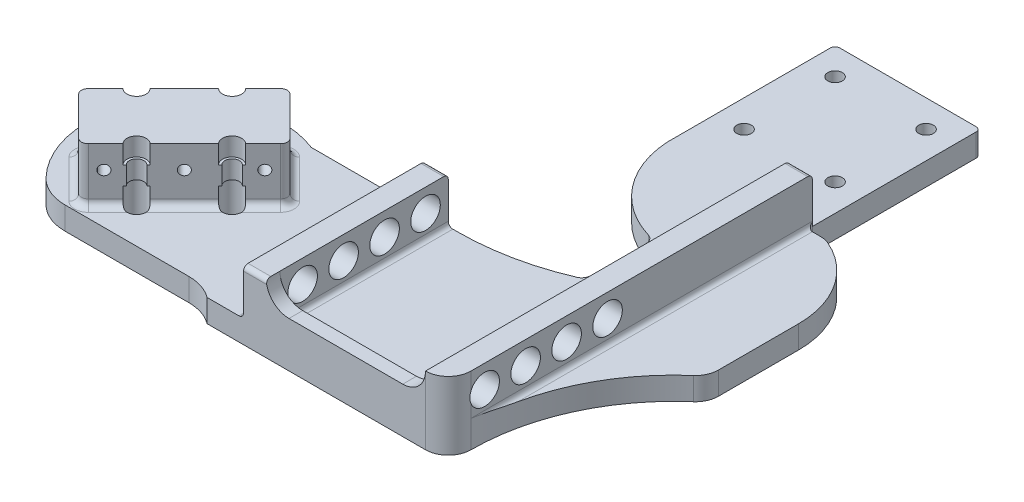
SolidWorks part; units mm, degrees
ref_plane "Спереди" through (0, 0, 0) normal (0, 0, 1) x (1, 0, 0)
ref_plane "Сверху" through (0, 0, 0) normal (0, 1, 0) x (1, 0, 0)
ref_plane "Справа" through (0, 0, 0) normal (1, 0, 0) x (0, 0, -1)
sketch "Эскиз2" plane through (0, 0, 0) normal (0, 1, 0) x (1, 0, 0)
  line L0 (0, 0) -> (32, 0)
  line L1 (0, 0) -> (0, 88)
  line L2 (32, 0) -> (32, 88)
  line L3 (0, 88) -> (32, 88)
  dimension "D1" = 88
  dimension "D2" = 32
extrude "Бобышка-Вытянуть1" add sketch "Эскиз2" along normal blind 5
sketch "Эскиз9" plane through (0, 5, 0) normal (0, 1, 0) x (1, 0, 0)
  line L0 (32, 10) -> (32, -30)
  line L1 (32, 10) -> (-68, 10)
  line L2 (32, -30) -> (-68, -30)
  line L3 (-68, 10) -> (-68, -30)
  line L4 (32, 0) -> (32, 88) construction
  line L5 (-68, -10) -> (32, -10) construction
  line L6 (32, 88) -> (0, 88) construction
  dimension "D1" = 98
  dimension "D2" = 40
  dimension "D3" = 100
extrude "Бобышка-Вытянуть6" add sketch "Эскиз9" against normal blind 5
sketch "Эскиз11" plane through (0, 5, 0) normal (0, 1, 0) x (1, 0, 0)
  line L0 (-46, -10) -> (-46, -20.5) construction
  line L1 (-46, -10) -> (-46, 0.5) construction
  line L6 (-68, -10) -> (32, -10) construction
  line L7 (-68, 10) -> (-68, -30) construction
  line L8 (32, -30) -> (32, 88) construction
  circle A0 centre (-46, -10) radius 10.5 construction
  circle A1 centre (-46, 0.5) radius 2.1
  circle A2 centre (-35.5, -10) radius 2.1
  circle A3 centre (-46, -20.5) radius 2.1
  circle A4 centre (-56.5, -10) radius 2.1
  dimension "D1" = 22
  dimension "D3" = 21
  dimension "D4" = 4.2
  dimension "D5" = 4.2
  dimension "D6" = 4.2
  dimension "D2" = 4.2
extrude "Вырез-Вытянуть3" cut sketch "Эскиз11" against normal up to surface (5 mm away) up to face at (-12, 0, -22.6667)
sketch "Эскиз12" plane through (0, 0, 0) normal (0, -1, 0) x (1, 0, 0)
  circle A4 centre (-46, 20.5) radius 2.1 construction
  circle A5 centre (-35.5, 10) radius 2.1 construction
  circle A6 centre (-46, -0.5) radius 2.1 construction
  circle A7 centre (-56.5, 10) radius 2.1 construction
  circle A8 centre (-46, 10) radius 19.5
  circle A9 centre (-46, 10) radius 21.5
  circle A10 centre (-46, 20.5) radius 2.1 construction
  circle A11 centre (-35.5, 10) radius 2.1 construction
  circle A12 centre (-46, -0.5) radius 2.1 construction
  circle A13 centre (-56.5, 10) radius 2.1 construction
  circle A14 centre (-46, 10) radius 10.5 construction
  dimension "D1" = 39
  dimension "D2" = 43
extrude "Бобышка-Вытянуть7" add sketch "Эскиз12" along normal blind 8
sketch "Эскиз13" plane through (0, 5, 0) normal (0, 1, 0) x (1, 0, 0)
  line L0 (6, 81) -> (26, 81) construction
  line L1 (6, 81) -> (6, 61) construction
  line L2 (26, 81) -> (26, 61) construction
  line L3 (6, 61) -> (26, 61) construction
  line L4 (16, 81) -> (16, 61) construction
  line L5 (16, 88) -> (16, -30) construction
  line L6 (32, 88) -> (0, 88) construction
  line L7 (-68, -30) -> (32, -30) construction
  circle A0 centre (6, 81) radius 1.6
  circle A1 centre (6, 61) radius 1.6
  circle A2 centre (26, 61) radius 1.6
  circle A3 centre (26, 81) radius 1.6
  dimension "D4" = 3.2
  dimension "D5" = 3.2
  dimension "D6" = 3.2
  dimension "D7" = 3.2
  dimension "D1" = 20
  dimension "D2" = 20
  dimension "D3" = 7
extrude "Вырез-Вытянуть4" cut sketch "Эскиз13" against normal through all
sketch "Sketch1" plane through (0, 0, -88) normal (0, 0, -1) x (-1, 0, 0)
  line L4 (-32, 0) -> (0, 0)
  line L5 (0, 0) -> (0, 5)
  line L6 (0, 5) -> (-32, 5)
  line L7 (-32, 5) -> (-32, 0)
  line L8 (-32, 0) -> (0, 0)
  line L9 (0, 0) -> (0, 5)
  line L10 (0, 5) -> (-32, 5)
  line L11 (-32, 5) -> (-32, 0)
  dimension "D1" = 0
extrude "Cut-Extrude1" cut sketch "Sketch1" against normal blind 1
sketch "Эскиз14" plane through (0, 0, 0) normal (0, -1, 0) x (1, 0, 0)
  line L3 (-53.8899, 30) -> (-68, 30)
  line L4 (-68, 30) -> (-68, -10)
  line L5 (-68, -10) -> (-53.8899, -10)
  line L6 (-53.8899, 30) -> (-68, 30)
  line L7 (-68, 30) -> (-68, -10)
  line L8 (-68, -10) -> (-53.8899, -10)
  arc A1 (-53.8899, 30) -> (-53.8899, -10) centre (-46, 10) ccw
  arc A2 (-53.8899, 30) -> (-53.8899, -10) centre (-46, 10) ccw
  dimension "D1" = 0
extrude "Вырез-Вытянуть5" cut sketch "Эскиз14" against normal through all
sketch "Эскиз15" plane through (0, 0, 0) normal (0, 1, 0) x (1, 0, 0)
  line L1 (-38.1101, -30) -> (-53.8899, -30)
  line L2 (-38.1101, -30) -> (-53.8899, -30)
  line L3 (-53.8899, 10) -> (-38.1101, 10)
  line L4 (-53.8899, 10) -> (-38.1101, 10)
  arc A1 (-53.8899, -30) -> (-38.1101, -30) centre (-46, -10) ccw
  arc A2 (-53.8899, -30) -> (-38.1101, -30) centre (-46, -10) ccw
  arc A3 (-38.1101, 10) -> (-53.8899, 10) centre (-46, -10) ccw
  arc A4 (-38.1101, 10) -> (-53.8899, 10) centre (-46, -10) ccw
  dimension "D1" = 0
  dimension "D2" = 0
extrude "Бобышка-Вытянуть8" add sketch "Эскиз15" along normal up to surface (5 mm away) up to face at (-46, 5, 1.6)
sketch "Эскиз16" plane through (0, 5, 0) normal (0, 1, 0) x (1, 0, 0)
  line L0 (-13, 10) -> (-8, 10)
  line L1 (-13, 10) -> (-13, -30)
  line L2 (-8, 10) -> (-8, -30)
  line L3 (-13, -30) -> (-8, -30)
  line L4 (0, 10) -> (-38.1101, 10) construction
  line L5 (-38.1101, -30) -> (32, -30) construction
  line L6 (32, -30) -> (32, 87) construction
  line L7 (27, -30) -> (32, -30)
  line L8 (27, -30) -> (27, 50)
  line L9 (32, -30) -> (32, 50)
  line L10 (27, 50) -> (32, 50)
  dimension "D1" = 5
  dimension "D2" = 45
  dimension "D3" = 5
  dimension "D4" = 80
extrude "Бобышка-Вытянуть9" add sketch "Эскиз16" along normal blind 10
sketch "Эскиз17" plane through (0, 5, 0) normal (0, 1, 0) x (1, 0, 0)
  line L0 (-8, -30) -> (-8, -27)
  line L1 (-8, -30) -> (27, -30)
  line L2 (-8, -27) -> (27, -27)
  line L3 (27, -30) -> (27, -27)
  line L4 (-8, -30) -> (-8, 10) construction
  line L5 (27, 50) -> (27, -30) construction
  dimension "D1" = 3
extrude "Бобышка-Вытянуть10" add sketch "Эскиз17" along normal blind 5
sketch "Эскиз18" plane through (-8, 0, 0) normal (1, 0, 0) x (0, 0, -1)
  line L0 (10, 10) -> (-41.8716, 10) construction
  line L1 (10, 15) -> (10, 5) construction
  circle A0 centre (5, 10) radius 3.25
  circle A1 centre (-4, 10) radius 3.25
  circle A2 centre (-13, 10) radius 3.25
  circle A3 centre (-22, 10) radius 3.25
  dimension "D1" = 6.5
  dimension "D2" = 6.5
  dimension "D3" = 6.5
  dimension "D4" = 6.5
  dimension "D5" = 5
  dimension "D6" = 9
  dimension "D7" = 9
  dimension "D8" = 9
extrude "Вырез-Вытянуть6" cut sketch "Эскиз18" against normal through all
sketch "Эскиз19" plane through (32, 0, 0) normal (1, 0, 0) x (0, 0, -1)
  line L0 (50, 10) -> (-21.4049, 10) construction
  line L1 (50, 15) -> (50, 5) construction
  circle A0 centre (41, 10) radius 3.25
  circle A1 centre (32, 10) radius 3.25
  circle A2 centre (23, 10) radius 3.25
  circle A3 centre (14, 10) radius 3.25
  dimension "D1" = 6.5
  dimension "D2" = 6.5
  dimension "D3" = 6.5
  dimension "D4" = 6.5
  dimension "D5" = 9
  dimension "D6" = 9
  dimension "D7" = 9
  dimension "D8" = 9
fillet "Скругление5" radius 1 4 edges at (27, 5, -11.5) (9.5, 5, 27)
fillet "Скругление6" radius 5 2 edges at (27, 10, 28.5) (-8, 10, 28.5)
fillet "Скругление7" radius 1 2 edges at (32, 2.5, -87) (0, 2.5, -87)
fillet "Скругление8" radius 1 3 edges at (-10.5, 15, 30) (-10.5, 15, -10) (29.5, 15, -50)
sketch "Эскиз20" plane through (0, -8, 0) normal (0, -1, 0) x (1, 0, 0)
  circle A1 centre (-46, 10) radius 21.5
  circle A2 centre (-46, 10) radius 21.5
  dimension "D1" = 0
extrude "Вырез-Вытянуть8" cut sketch "Эскиз20" against normal up to surface (8 mm away) up to face at (-46, 0, -2.6)
sketch "Эскиз21" plane through (0, 5, 0) normal (0, 1, 0) x (1, 0, 0)
  line L0 (-57.758, -28) -> (-27, -28)
  line L1 (-38.1101, -30) -> (-14, -30) construction
  line L2 (-13, 10) -> (-13, -30) construction
  line L3 (-38.1101, -30) -> (-21, -30)
  arc A0 (-38.1101, 10) -> (-38.1101, -30) centre (-46, -10) ccw construction
  arc A1 (-27, -28) -> (-21, -30) centre (-27, -38) cw
  arc A2 (-57.758, -28) -> (-38.1101, -30) centre (-46, -10) ccw
  dimension "D1" = 2
  dimension "D2" = 10
  dimension "D3" = 8
extrude "Вырез-Вытянуть9" cut sketch "Эскиз21" against normal through all
fillet "Скругление9" radius 10 1 edges at (-57.758, 2.5, 28)
sketch "Эскиз22" plane through (0, 0, 0) normal (-1, 0, 0) x (0, 0, 1)
  line L0 (-50, 14) -> (-50, 6) construction
  line L1 (-50, 5) -> (-50, 0) construction
  line L2 (-86, 5) -> (-10, 5) construction
  line L3 (-86, 0) -> (-10, 0) construction
  line L4 (-50, 5) -> (-10, 5)
  line L5 (-50, 0) -> (-10, 0)
  line L6 (-10, 0) -> (-10, 5) construction
  line L7 (-10, 0) -> (-10, 5)
  line L8 (-50, 5) -> (-50, 0)
extrude "Вырез-Вытянуть10" cut sketch "Эскиз22" against normal blind 17
sketch "Эскиз23" plane through (32, 0, 0) normal (1, 0, 0) x (0, 0, -1)
  line L4 (10, 5) -> (10, 0)
  line L5 (50, 5) -> (10, 5)
  line L6 (50, 0) -> (50, 5)
  line L7 (10, 0) -> (50, 0)
  line L8 (10, 5) -> (10, 0)
  line L9 (50, 5) -> (10, 5)
  line L10 (50, 0) -> (50, 5)
  line L11 (10, 0) -> (50, 0)
  dimension "D1" = 0
extrude "Бобышка-Вытянуть11" add sketch "Эскиз23" along normal blind 17
sketch "Эскиз25" plane through (0, 5, 0) normal (0, 1, 0) x (1, 0, 0)
  line L0 (17, 15) -> (17, 10)
  line L1 (17, 10) -> (17, 50) construction
  line L2 (17, 10) -> (-6, 10)
  line L3 (17, 10) -> (-7, 10) construction
  line L6 (17, 30) -> (17, 50)
  line L7 (17, 50) -> (0, 50)
  arc A0 (17, 30) -> (0, 50) centre (21.9531, 51.4352) cw
  arc A1 (17, 15) -> (-6, 10) centre (-6, 65.4) cw
  dimension "D4" = 22
  dimension "D1" = 5
  dimension "D2" = 23
  dimension "D3" = 15
  dimension "D5" = 20
extrude "Бобышка-Вытянуть12" add sketch "Эскиз25" against normal up to surface (5 mm away) up to face at (4.4666, 0, -26.743)
fillet "Скругление10" radius 2 2 edges at (17, 2.5, -15) (17, 2.5, -30)
sketch "Эскиз26" plane through (0, 5, 0) normal (0, 1, 0) x (1, 0, 0)
  line L0 (32, 30) -> (49, 30) construction
  line L1 (32, 50) -> (32, 10) construction
  line L3 (49, 50) -> (49, 10) construction
  line L4 (32, 50) -> (32, 30) construction
  line L5 (49, 50) -> (32, 50) construction
  line L6 (49, 50) -> (32, 50)
  line L7 (49, 50) -> (49, 30)
  arc A0 (49, 30) -> (32, 50) centre (28.7353, 30) ccw
  dimension "D1" = 20
extrude "Вырез-Вытянуть11" cut sketch "Эскиз26" against normal through all
sketch "Эскиз27" plane through (0, 5, 0) normal (0, 1, 0) x (1, 0, 0)
  line L0 (49, 10) -> (32, 10) construction
  line L1 (49, 10) -> (32, 10)
  line L2 (32, 10) -> (32, -25)
  arc A0 (49, 10) -> (32, -25) centre (76.5294, -25) ccw
  dimension "D1" = 35
extrude "Бобышка-Вытянуть13" add sketch "Эскиз27" against normal up to surface (5 mm away) up to face at (5.1363, 0, -23.6939)
fillet "Скругление12" radius 5 1 edges at (32, 7.5, 30)
fillet "Скругление13" radius 1 1 edges at (32, 5, -12.5)
sketch "Эскиз28" plane through (32, 0, 0) normal (1, 0, 0) x (0, 0, -1)
  circle A0 centre (5, 10) radius 3.25 construction
  circle A1 centre (-4, 10) radius 3.25 construction
  circle A2 centre (-13, 10) radius 3.25 construction
  circle A3 centre (-22, 10) radius 3.25 construction
  circle A4 centre (5, 10) radius 3.25
  circle A5 centre (-4, 10) radius 3.25
  circle A6 centre (-13, 10) radius 3.25
  circle A7 centre (-22, 10) radius 3.25
extrude "Вырез-Вытянуть12" cut sketch "Эскиз28" against normal up to surface (5 mm away) up to face at (27, 11.2414, -19.0414)
fillet "Скругление14" radius 5 1 edges at (49, 2.5, -10)
sketch "Эскиз29" plane through (0, 0, -50) normal (0, 0, -1) x (-1, 0, 0)
  line L0 (-32, 0) -> (-32, 5) construction
  line L1 (-32, 0) -> (-32, 8)
  line L2 (-32, 14) -> (-32, 6) construction
  line L3 (-32, 8) -> (-37, 8)
  line L4 (-37, 8) -> (-37, 0)
  line L5 (-37, 0) -> (-32, 0)
  dimension "D1" = 5
  dimension "D2" = 8
extrude "Вырез-Вытянуть13" cut sketch "Эскиз29" against normal blind 1
fillet "Скругление15" radius 1 1 edges at (32, 3, -49)
fillet "Скругление16" radius 5 1 edges at (35.7822, 2.5, -49)
sketch "Эскиз30" plane through (0, 5, 0) normal (0, 1, 0) x (1, 0, 0)
  line L0 (-52.364, -26.864) -> (-62.864, -16.364)
  line L1 (-52.364, -26.864) -> (-47.4849, -21.9849)
  line L2 (-62.864, -16.364) -> (-57.9849, -11.4849)
  line L3 (-29.136, -3.636) -> (-39.636, 6.864)
  line L4 (-46, -20.5) -> (-55.0151, -11.4849) construction
  line L5 (-36.9849, -8.5151) -> (-44.5151, -0.9849) construction
  line L6 (-44.5151, -19.0151) -> (-36.9849, -11.4849)
  line L7 (-34.0151, -8.5151) -> (-29.136, -3.636)
  line L8 (-44.5151, 1.9849) -> (-39.636, 6.864)
  line L9 (-55.0151, -8.5151) -> (-47.4849, -0.9849)
  line L10 (-47.4849, -21.9849) -> (-34.0151, -8.5151) construction
  line L11 (-57.9849, -11.4849) -> (-44.5151, 1.9849) construction
  circle A0 centre (-46, 0.5) radius 2.1 construction
  circle A1 centre (-56.5, -10) radius 2.1 construction
  circle A2 centre (-46, -20.5) radius 2.1 construction
  circle A3 centre (-35.5, -10) radius 2.1 construction
  arc A4 (-47.4849, -0.9849) -> (-44.5151, 1.9849) centre (-46, 0.5) ccw
  arc A5 (-57.9849, -11.4849) -> (-55.0151, -8.5151) centre (-56.5, -10) ccw
  arc A6 (-44.5151, -19.0151) -> (-47.4849, -21.9849) centre (-46, -20.5) ccw
  arc A7 (-34.0151, -8.5151) -> (-36.9849, -11.4849) centre (-35.5, -10) ccw
  dimension "D1" = 9
  dimension "D2" = 14.8492
  dimension "D3" = 9
extrude "Бобышка-Вытянуть14" add sketch "Эскиз30" along normal blind 12
fillet "Скругление17" radius 1.5 12 edges at (-34.386, 5, -1.614) (-49.9244, 5, 24.4244) (-29.136, 11, 3.636) (-31.5756, 5, 6.0756) (-40.75, 5, 15.25) (-39.636, 11, -6.864) (-42.0756, 5, -4.4244) (-51.25, 5, 4.75) (-60.4244, 5, 13.9244) (-57.614, 5, 21.614) (-52.364, 11, 26.864) (-62.864, 11, 16.364)
sketch "Эскиз32" plane through (-23.25, 0, -23.25) normal (-0.7071, 0, -0.7071) x (-0.7071, 0, 0.7071)
  line L0 (24.6734, 13) -> (54.5226, 13) construction
  line L3 (24.6734, 17) -> (24.6734, 6.5) construction
  line L4 (54.5226, 6.5) -> (54.5226, 17) construction
  line L5 (34.2734, 17) -> (44.9226, 17) construction
  dimension "D1" = 4
ref_plane "Плоскость1" through (0, 13, 0) normal (0, -1, 0) x (-0.7071, 0, 0.7071)
sketch "Эскиз33" plane through (0, 13, 0) normal (0, -1, 0) x (-0.7071, 0, 0.7071)
  line L0 (30.0734, 32.8805) -> (30.5734, 32.8805)
  line L1 (33.7734, 32.8805) -> (34.2734, 32.8805)
  line L2 (44.9226, 32.8805) -> (45.4226, 32.8805)
  line L3 (48.6226, 32.8805) -> (49.1226, 32.8805)
  line L4 (56.0226, 31.3805) -> (56.0226, 19.5312) construction
  line L5 (23.1734, 19.5312) -> (23.1734, 31.3805) construction
  line L6 (56.0226, 31.3805) -> (56.0226, 19.5312) construction
  line L7 (23.1734, 19.5312) -> (23.1734, 31.3805) construction
  line L8 (23.1734, 25.4558) -> (56.0226, 25.4558) construction
  line L9 (48.6226, 18.0312) -> (49.1226, 18.0312)
  line L10 (44.9226, 18.0312) -> (45.4226, 18.0312)
  line L11 (33.7734, 18.0312) -> (34.2734, 18.0312)
  line L12 (30.0734, 18.0312) -> (30.5734, 18.0312)
  arc A0 (30.0734, 32.8805) -> (34.2734, 32.8805) centre (32.1734, 32.8805) ccw construction
  arc A1 (30.0734, 32.8805) -> (34.2734, 32.8805) centre (32.1734, 32.8805) ccw
  arc A2 (44.9226, 32.8805) -> (49.1226, 32.8805) centre (47.0226, 32.8805) ccw construction
  arc A3 (44.9226, 32.8805) -> (49.1226, 32.8805) centre (47.0226, 32.8805) ccw
  arc A4 (30.5734, 32.8805) -> (33.7734, 32.8805) centre (32.1734, 32.8805) ccw
  arc A5 (45.4226, 32.8805) -> (48.6226, 32.8805) centre (47.0226, 32.8805) ccw
  arc A6 (45.4226, 18.0312) -> (48.6226, 18.0312) centre (47.0226, 18.0312) cw
  arc A7 (30.5734, 18.0312) -> (33.7734, 18.0312) centre (32.1734, 18.0312) cw
  arc A8 (44.9226, 18.0312) -> (49.1226, 18.0312) centre (47.0226, 18.0312) cw
  arc A9 (30.0734, 18.0312) -> (34.2734, 18.0312) centre (32.1734, 18.0312) cw
  dimension "D1" = 0.5
  dimension "D2" = 0.5
extrude "Бобышка-Вытянуть15" add sketch "Эскиз33" along normal blind 4
sketch "Эскиз34" plane through (-23.25, 0, -23.25) normal (-0.7071, 0, -0.7071) x (-0.7071, 0, 0.7071)
  circle A1 centre (52.0984, 12) radius 1.1
  circle A2 centre (52.0984, 12) radius 1.1
  circle A3 centre (39.5984, 12) radius 1.1
  circle A4 centre (39.5984, 12) radius 1.1
  circle A5 centre (27.0984, 12) radius 1.1
  circle A6 centre (27.0984, 12) radius 1.1
  dimension "D1" = 0
  dimension "D2" = 0
  dimension "D3" = 0
extrude "Вырез-Вытянуть14" cut sketch "Эскиз34" against normal up to surface (14.8492 mm away) up to face at (-48.3511, 11.375, 22.8511)
